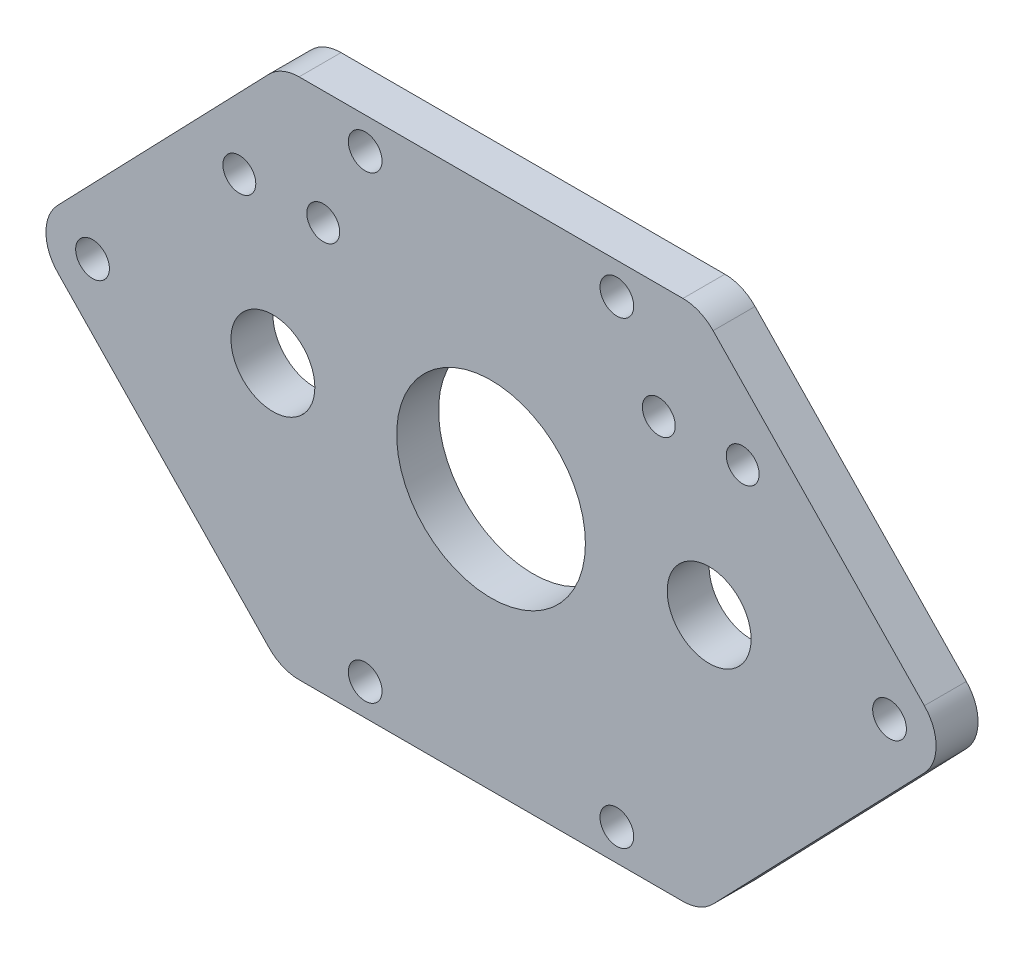
SolidWorks part; units mm, degrees
material "6061-T6 (SS)"
ref_plane "Front Plane" through (0, 0, 0) normal (0, 0, 1) x (1, 0, 0)
ref_plane "Top Plane" through (0, 0, 0) normal (0, 1, 0) x (1, 0, 0)
ref_plane "Right Plane" through (0, 0, 0) normal (1, 0, 0) x (0, 0, -1)
sketch "Sketch5" plane through (0, 0, 0) normal (0, 0, 1) x (1, 0, 0)
  line L0 (-19.7318, -15.9943) -> (19.7318, 15.9943) construction
  line L1 (0, 0) -> (25.4, 0) construction
  line L2 (-19.05, 34.7624) -> (19.05, 34.7624) construction
  line L3 (-31.75, -39.5249) -> (31.75, -39.5249)
  line L5 (-31.75, 39.5249) -> (31.75, 39.5249)
  line L7 (-31.75, -39.5249) -> (31.75, 39.5249) construction
  line L8 (-31.75, 39.5249) -> (31.75, -39.5249) construction
  line L9 (-39.37, 0) -> (39.37, 0) construction
  line L10 (-19.05, -34.7624) -> (19.05, -34.7624) construction
  line L11 (0, 39.5249) -> (0, -39.5249) construction
  line L12 (31.75, -39.5249) -> (-31.75, -39.5249)
  line L16 (-39.37, -12.7) -> (39.37, -12.7) construction
  line L17 (-39.37, -12.7) -> (-39.37, -10.4954) construction
  line L18 (-39.37, 12.7) -> (39.37, 12.7) construction
  line L19 (39.37, -12.7) -> (39.37, 0) construction
  line L20 (-39.37, -12.7) -> (39.37, 12.7) construction
  line L21 (-39.37, 12.7) -> (39.37, -12.7) construction
  line L22 (-31.75, 39.5249) -> (-69.85, 0)
  line L23 (-31.75, -39.5249) -> (-69.85, 0)
  line L24 (0, 39.5249) -> (0, -39.5249) construction
  line L25 (31.75, -39.5249) -> (69.85, 0)
  line L26 (31.75, 39.5249) -> (69.85, 0)
  line L28 (-39.37, 0) -> (-39.37, 12.7) construction
  line L29 (39.37, 2.9966) -> (39.37, 12.7) construction
  line L31 (69.85, 0) -> (31.75, -39.5249)
  line L33 (-38.1, 22.225) -> (-25.4, 22.225) construction
  line L38 (-31.75, 12.7) -> (-31.75, 28.575) construction
  line L39 (-57.6079, 12.7) -> (57.6079, 12.7) construction
  line L40 (-19.05, 12.7) -> (-44.45, 12.7) construction
  line L41 (-19.05, 12.7) -> (-19.05, 28.575) construction
  line L42 (-19.05, 28.575) -> (-44.45, 28.575) construction
  line L43 (-44.45, 12.7) -> (-44.45, 28.575) construction
  line L44 (-19.05, 15.875) -> (-44.45, 15.875) construction
  circle A0 centre (0, 0) radius 14.2875
  circle A1 centre (0, 0) radius 25.4 construction
  circle A6 centre (-19.05, 34.7624) radius 2.5527
  circle A7 centre (19.05, 34.7624) radius 2.5527
  circle A8 centre (19.05, -34.7624) radius 2.5527
  circle A9 centre (-19.05, -34.7624) radius 2.5527
  circle A18 centre (60.325, 0) radius 2.5527
  circle A19 centre (-60.325, 0) radius 2.5527
  circle A21 centre (-33.02, 0) radius 6.35
  circle A22 centre (33.02, 0) radius 6.35
  circle A25 centre (-38.1, 22.225) radius 2.4892
  circle A26 centre (-25.4, 22.225) radius 2.4892
  circle A29 centre (25.4, 22.225) radius 2.4892
  circle A30 centre (38.1, 22.225) radius 2.4892
  point P8 (0, 0)
  point P19 (0, 34.7624)
  point P37 (0, -25.4)
  point P59 (-31.75, 22.225)
  dimension "D1" = 28.575
  dimension "D2" = 5.1054
  dimension "D3" = 50.8
  dimension "D5" = 19.05
  dimension "D6" = 5.1054
  dimension "D8" = 4.7625
  dimension "D11" = 12.7
  dimension "D12" = 25.4
  dimension "D13" = 60.325
  dimension "D14" = 60.325
  dimension "D10" = 2
  dimension "D16" = 33.02
  dimension "D17" = 12.7
  dimension "D18" = 4.9784
  dimension "D19" = 9.525
  dimension "D23" = 25.4
  dimension "D4" = 34.7624
  dimension "45" = 39.028
  dimension "D7" = 4.7625
  dimension "D9" = 25.4
  dimension "D15" = 69.85
  dimension "D20" = 3.175
  dimension "D21" = 12.7
  dimension "D22" = 15.875
  dimension "D24" = 63.5
extrude "Boss-Extrude1" add sketch "Sketch5" along normal blind 6.35 contours L3 | A21 L22 L23 A19 | A22 L5 A21 L3 A9 A0 A6 A7 A8 | L26 A22 L25 A18 region at (-49.6443, -18.6485, 0)
fillet "Fillet2" radius 6.35 6 edges at (31.75, -39.5249, 3.175) (-31.75, -39.5249, 3.175) (31.75, 39.5249, 3.175) (-31.75, 39.5249, 3.175) (69.85, 0, 3.175) (-69.85, 0, 3.175)
equation "\"NEO\"= 60mm"
